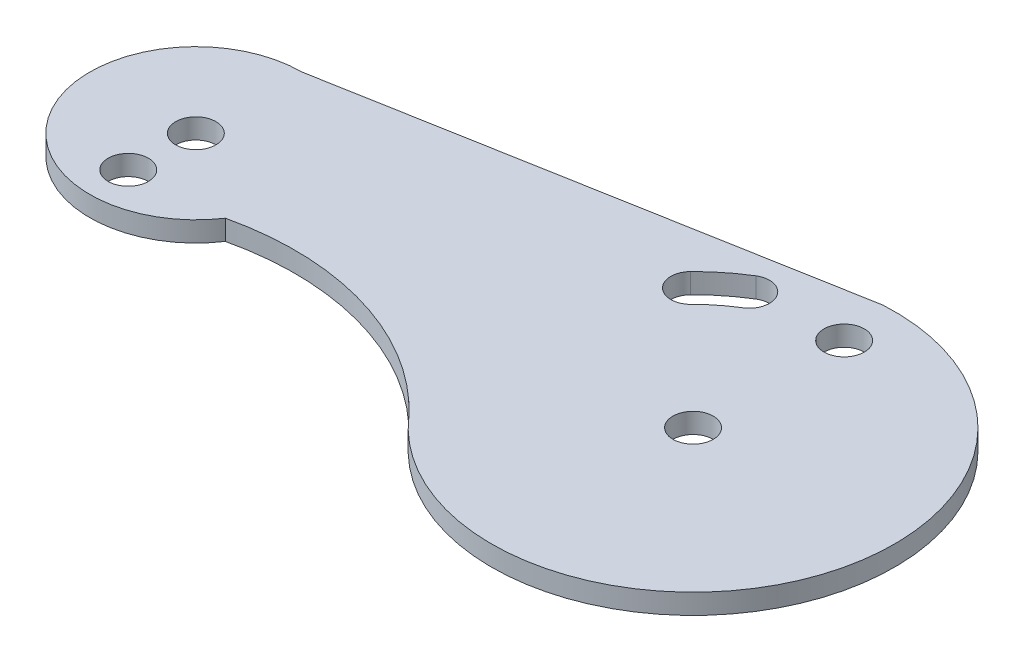
SolidWorks part; units mm, degrees
ref_plane "Front Plane" through (0, 0, 0) normal (0, 0, 1) x (1, 0, 0)
ref_plane "Top Plane" through (0, 0, 0) normal (0, 1, 0) x (1, 0, 0)
ref_plane "Right Plane" through (0, 0, 0) normal (1, 0, 0) x (0, 0, -1)
sketch "Sketch1" plane through (0, 0, 0) normal (0, 1, 0) x (1, 0, 0)
  line L0 (-33.676, 11.1806) -> (15.2114, 19.9842)
  line L1 (3.3343, 7.5122) -> (16.3199, 0.0149) construction
  line L2 (16.3199, 0.0149) -> (-18.5385, 0.0149) construction
  circle A0 centre (-33.676, 0.6496) radius 2
  arc A1 (1.2118, -13.0902) -> (15.2114, 19.9842) centre (16.3199, 0.0149) ccw
  arc A3 (8.4703, 12.7906) -> (6.3788, 16.1947) centre (7.4245, 14.4927) ccw
  arc A4 (-24.9124, -5.1898) -> (1.2118, -13.0902) centre (-18.722, -31.8627) cw
  arc A6 (-33.676, 11.1806) -> (-24.9124, -5.1898) centre (-33.676, 0.6496) ccw
  circle A7 centre (-33.8862, -5.847) radius 2
  circle A8 centre (16.3199, 0.0149) radius 2
  circle A9 centre (16.3199, 15.0149) radius 2
  arc A10 (2.7751, 13.3247) -> (5.6248, 10.5244) centre (4.2, 11.9246) ccw
  arc A11 (8.4703, 12.7906) -> (5.6248, 10.5244) centre (16.3199, 0.0149) ccw
  arc A12 (6.3788, 16.1947) -> (2.7751, 13.3247) centre (16.3199, 0.0149) ccw
  point P11 (-24.9124, -5.1898)
  point P26 (16.3266, 0.0086)
  dimension "D1" = 4
  dimension "D2" = 40
  dimension "D3" = 30
  dimension "D6" = 4
  dimension "D7" = 4
  dimension "D8" = 4
  dimension "D5" = 50
  dimension "D10" = 15
  dimension "D11" = 6.5
extrude "Boss-Extrude2" add sketch "Sketch1" along normal blind 2
